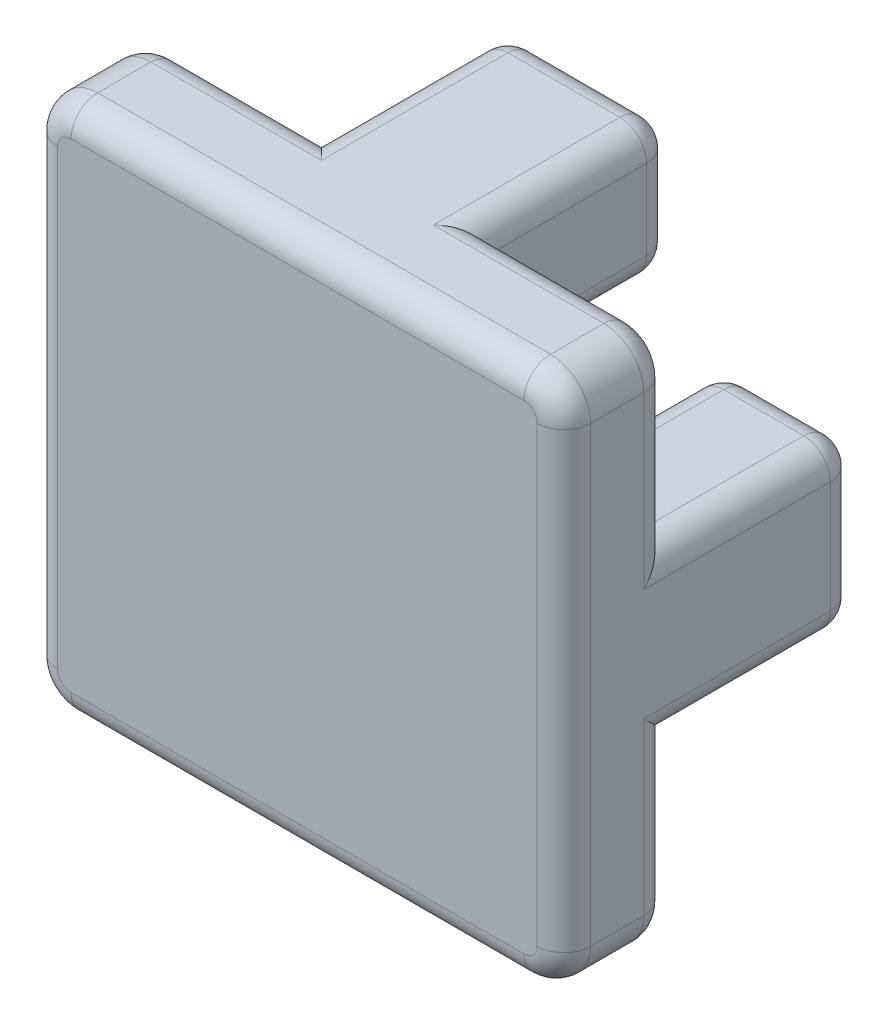
SolidWorks part; units mm, degrees
ref_plane "Спереди" through (0, 0, 0) normal (0, 0, 1) x (1, 0, 0)
ref_plane "Сверху" through (0, 0, 0) normal (0, 1, 0) x (1, 0, 0)
ref_plane "Справа" through (0, 0, 0) normal (1, 0, 0) x (0, 0, -1)
other "Configuration Table"
sketch "Эскиз2" plane through (0, 0, 0) normal (0, 0, 1) x (1, 0, 0)
  line L0 (10, 3) -> (10, 8.5) construction
  line L1 (10, 3.1) -> (5, 3.1)
  line L2 (10, 3.1) -> (10, -3.1)
  line L3 (10, -3.1) -> (5, -3.1)
  line L4 (5, 3.1) -> (5, -3.1)
  line L5 (11, -1.8) -> (11, 1.8) construction
  line L6 (8.5, 3) -> (10, 3) construction
  line L7 (3.1, -10) -> (3.1, -5)
  line L8 (3.1, -10) -> (-3.1, -10)
  line L9 (-3.1, -10) -> (-3.1, -5)
  line L10 (3.1, -5) -> (-3.1, -5)
  line L11 (-10, -3.1) -> (-5, -3.1)
  line L12 (-10, -3.1) -> (-10, 3.1)
  line L13 (-10, 3.1) -> (-5, 3.1)
  line L14 (-5, -3.1) -> (-5, 3.1)
  line L15 (-3.1, 10) -> (-3.1, 5)
  line L16 (-3.1, 10) -> (3.1, 10)
  line L17 (3.1, 10) -> (3.1, 5)
  line L18 (-3.1, 5) -> (3.1, 5)
  line L19 (3, -10) -> (8.5, -10) construction
  point P8 (11, 0)
  point P9 (10, 0)
  dimension "D1" = 1
  dimension "D2" = 0.1
  dimension "D3" = 5
  dimension "D4" = 4
extrude "Бобышка-Вытянуть1" add sketch "Эскиз2" against normal blind 7
sketch "Эскиз5" plane through (0, 0, 0) normal (0, 0, 1) x (1, 0, 0)
  line L0 (-3, 10) -> (-8.5, 10) construction
  line L1 (-10, -3) -> (-10, -8.5) construction
  line L2 (3, -10) -> (8.5, -10) construction
  line L3 (10, 3) -> (10, 8.5) construction
  line L4 (8.5, 10) -> (-8.5, 10)
  line L5 (-10, 8.5) -> (-10, -8.5)
  line L6 (-8.5, -10) -> (8.5, -10)
  line L7 (10, -8.5) -> (10, 8.5)
  arc A0 (-8.5, 10) -> (-10, 8.5) centre (-8.5, 8.5) ccw construction
  arc A1 (-10, -8.5) -> (-8.5, -10) centre (-8.5, -8.5) ccw construction
  arc A2 (8.5, -10) -> (10, -8.5) centre (8.5, -8.5) ccw construction
  arc A3 (10, 8.5) -> (8.5, 10) centre (8.5, 8.5) ccw construction
  arc A4 (-8.5, 10) -> (-10, 8.5) centre (-8.5, 8.5) ccw
  arc A5 (-10, -8.5) -> (-8.5, -10) centre (-8.5, -8.5) ccw
  arc A6 (8.5, -10) -> (10, -8.5) centre (8.5, -8.5) ccw
  arc A7 (10, 8.5) -> (8.5, 10) centre (8.5, 8.5) ccw
extrude "Бобышка-Вытянуть2" add sketch "Эскиз5" along normal blind 4
fillet "Скругление1" radius 1 52 edges at (-3.1, 10, -3.5) (-10, 3.1, -3.5) (-10, -3.1, -3.5) (-3.1, -10, -3.5) (3.1, -10, -3.5) (10, -3.1, -3.5) (10, 3.1, -3.5) (3.1, 10, -3.5) (0, 10, 4) (9.5607, 9.5607, 4) (10, 0, 4) (9.5607, -9.5607, 4) (0, -10, 4) (-9.5607, -9.5607, 4) (-10, 0, 4) (-9.5607, 9.5607, 4) (-5.8, 10, 0) (-9.5607, 9.5607, 0) (-10, 5.8, 0) (-10, -5.8, 0) (-9.5607, -9.5607, 0) (-5.8, -10, 0) (5.8, -10, 0) (9.5607, -9.5607, 0) (10, -5.8, 0) (10, 5.8, 0) (9.5607, 9.5607, 0) (5.8, 10, 0) (3.1, 5, -3.5) (-3.1, 5, -3.5) (5, -3.1, -3.5) (5, 3.1, -3.5) (-3.1, -5, -3.5) (3.1, -5, -3.5) (-5, 3.1, -3.5) (-5, -3.1, -3.5) (7.5, 3.1, -7) (5, 0, -7) (7.5, -3.1, -7) (10, 0, -7) (3.1, -7.5, -7) (0, -5, -7) (-3.1, -7.5, -7) (0, -10, -7) (-7.5, -3.1, -7) (-5, 0, -7) (-7.5, 3.1, -7) (-10, 0, -7) (-3.1, 7.5, -7) (0, 5, -7) (3.1, 7.5, -7) (0, 10, -7)
